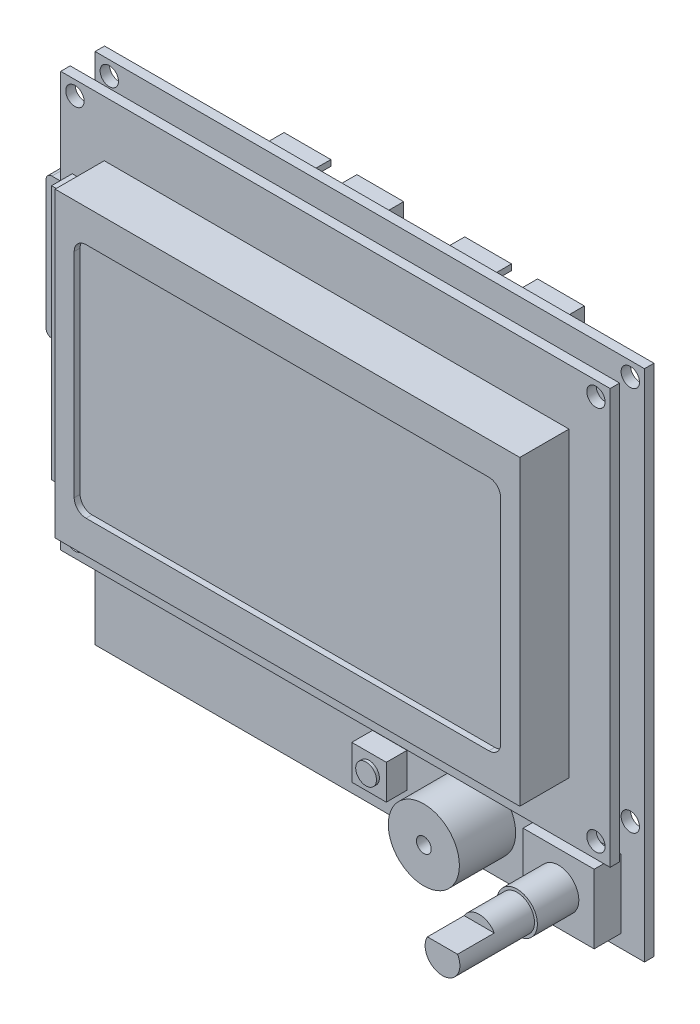
SolidWorks part; units mm, degrees
ref_plane "Front Plane" through (0, 0, 0) normal (0, 0, 1) x (1, 0, 0)
ref_plane "Top Plane" through (0, 0, 0) normal (0, 1, 0) x (1, 0, 0)
ref_plane "Right Plane" through (0, 0, 0) normal (1, 0, 0) x (0, 0, -1)
sketch "Sketch1" plane through (0, 0, 0) normal (0, 0, 1) x (1, 0, 0)
  line L1 (-46.375, -43.375) -> (46.375, -43.375)
  line L2 (-46.375, -43.375) -> (-46.375, 43.375)
  line L3 (-46.375, 43.375) -> (46.375, 43.375)
  line L4 (46.375, -43.375) -> (46.375, 43.375)
  line L6 (-43.975, 40.975) -> (43.975, 40.975) construction
  line L7 (-43.975, 40.975) -> (-43.975, -24.025) construction
  line L8 (-43.975, -24.025) -> (43.975, -24.025) construction
  line L9 (43.975, 40.975) -> (43.975, -24.025) construction
  circle A0 centre (-43.975, 40.975) radius 1.55
  circle A1 centre (43.975, 40.975) radius 1.55
  circle A2 centre (43.975, -24.025) radius 1.55
  circle A3 centre (-43.975, -24.025) radius 1.55
  point P5 (0, 43.375)
  point P6 (-46.375, 0)
  dimension "D3" = 3.1
  dimension "D1" = 86.75
  dimension "D2" = 92.75
  dimension "D4" = 2.4
  dimension "D5" = 2.4
  dimension "D6" = 2.4
  dimension "D7" = 65
extrude "First PCB Extrude" add sketch "Sketch1" along normal blind 1.6
sketch "Sketch2" plane through (0, 0, 1.6) normal (0, 0, 1) x (1, 0, 0)
  line L0 (-46.375, -43.375) -> (46.375, -43.375) construction
  line L1 (-46.375, -43.375) -> (-46.375, 43.375) construction
  circle A0 centre (18.625, -35.375) radius 6
  dimension "D1" = 12
  dimension "D2" = 8
  dimension "D3" = 65
extrude "Speaker Extrude" add sketch "Sketch2" along normal blind 9.5
sketch "Sketch15" plane through (0, 0, 11.1) normal (0, 0, 1) x (1, 0, 0)
  circle A0 centre (18.625, -35.375) radius 1.25
  dimension "D1" = 2.5
extrude "Speaker Hole Cut" cut sketch "Sketch15" against normal blind 5
sketch "Sketch3" plane through (0, 0, 1.6) normal (0, 0, 1) x (-1, 0, 0)
  line L1 (-42.375, 41.2) -> (-30.375, 41.2)
  line L2 (-42.375, 41.2) -> (-42.375, 29.55)
  line L3 (-42.375, 29.55) -> (-30.375, 29.55)
  line L4 (-30.375, 41.2) -> (-30.375, 29.55)
  line L8 (-30.375, 35.375) -> (-18.625, 35.375) construction
  line L10 (-36.375, 41.2) -> (-36.375, 29.55) construction
  line L11 (-46.375, 43.375) -> (-46.375, -43.375) construction
  circle A1 centre (-18.625, 35.375) radius 6 construction
  point P19 (-13.8797, 31.7032)
  dimension "D1" = 11.65
  dimension "D2" = 12
  dimension "D3" = 10
extrude "Rotary Switch Base Extrude" add sketch "Sketch3" along normal blind 4.5
sketch "Sketch4" plane through (0, 0, 1.6) normal (0, 0, 1) x (-1, 0, 0)
  line L0 (-3.375, 38.29) -> (-3.375, 32.46) construction
  line L1 (-6.29, 38.29) -> (-0.46, 38.29)
  line L2 (-6.29, 38.29) -> (-6.29, 32.46)
  line L3 (-6.29, 32.46) -> (-0.46, 32.46)
  line L4 (-0.46, 38.29) -> (-0.46, 32.46)
  line L5 (-6.29, 35.375) -> (-0.46, 35.375) construction
  line L6 (-6.29, 35.375) -> (-18.625, 35.375) construction
  line L15 (-46.375, 43.375) -> (-46.375, -43.375) construction
  point P8 (-3.375, 35.375)
  dimension "D1" = 5.83
  dimension "D2" = 5.83
  dimension "D3" = 43
extrude "Reset Switch Base Extrude" add sketch "Sketch4" along normal blind 3.5
sketch "Sketch5" plane through (0, 0, 5.1) normal (0, 0, 1) x (-1, 0, 0)
  line L1 (-6.29, 38.29) -> (-0.46, 32.46) construction
  line L2 (-0.46, 38.29) -> (-6.29, 32.46) construction
  circle A0 centre (-3.375, 35.375) radius 1.75
  dimension "D1" = 3.5
extrude "Reset Button Extrude" add sketch "Sketch5" along normal blind 0.5
sketch "Sketch16" plane through (0, 0, 6.1) normal (0, 0, 1) x (1, 0, 0)
  line L0 (30.375, -29.55) -> (30.375, -41.2) construction
  line L1 (42.375, -29.55) -> (30.375, -29.55) construction
  circle A0 centre (36.375, -35.375) radius 3.415
  point P4 (30.375, -35.375)
  point P7 (36.375, -29.55)
  dimension "D1" = 6.83
extrude "Rotary Switch Bottom Extrude" add sketch "Sketch16" along normal blind 7
sketch "Sketch17" plane through (0, 0, 13.1) normal (0, 0, 1) x (1, 0, 0)
  circle A0 centre (36.375, -35.375) radius 2.935
  dimension "D1" = 5.87
extrude "Rotary Switch Middle Extrude" add sketch "Sketch17" along normal blind 6.4
sketch "Sketch18" plane through (0, 0, 19.5) normal (0, 0, 1) x (1, 0, 0)
  line L0 (33.8318, -33.91) -> (38.9182, -33.91)
  arc A0 (33.8318, -33.91) -> (38.9182, -33.91) centre (36.375, -35.375) ccw
  circle A1 centre (36.375, -35.375) radius 2.935 construction
  point P6 (36.375, -38.31)
  dimension "D1" = 4.4
extrude "Rotary Switch Top Extrude" add sketch "Sketch18" along normal offset from surface (6.2 mm away) 24.1 up to face at (36.375, -35.375, 1.6) offset beyond the face yes
sketch "Sketch9" plane through (0, 0, 0) normal (0, 0, -1) x (1, 0, 0)
  line L0 (-46.375, -43.375) -> (46.375, -43.375) construction
  line L1 (-46.125, 5.425) -> (-27.875, 5.425)
  line L2 (-46.125, 5.425) -> (-46.125, -20.975)
  line L3 (-46.125, -20.975) -> (-20.375, -20.975)
  line L4 (-20.375, 3.425) -> (-20.375, -20.975)
  line L6 (-20.375, 3.425) -> (-25.875, 3.425)
  line L7 (-25.875, 3.425) -> (-27.875, 5.425)
  line L8 (-46.375, -43.375) -> (-46.375, 43.375) construction
  dimension "D1" = 22.4
  dimension "D2" = 26.4
  dimension "D3" = 0.25
  dimension "D4" = 18.25
  dimension "D5" = 2
  dimension "D6" = 45
  dimension "D7" = 25.75
extrude "SD Card Slot Extrude" add sketch "Sketch9" along normal blind 3
sketch "Sketch19" plane through (0, 0, 1.6) normal (0, 0, 1) x (1, 0, 0)
  line L0 (-46.375, 43.375) -> (-46.375, -43.375) construction
  line L1 (-33.375, -22.875) -> (16.625, -22.875)
  line L2 (-33.375, -22.875) -> (-33.375, -25.375)
  line L3 (-33.375, -25.375) -> (16.625, -25.375)
  line L4 (16.625, -22.875) -> (16.625, -25.375)
  line L5 (-46.375, -43.375) -> (46.375, -43.375) construction
  dimension "D1" = 2.5
  dimension "D2" = 50
  dimension "D3" = 13
  dimension "D4" = 18
extrude "Connector Extrude" add sketch "Sketch19" along normal blind 4.2
sketch "Sketch11" plane through (0, -2, 5.8) normal (0, 0, -1) x (1, 0, 0)
  line L1 (46.375, 24.625) -> (-46.375, 24.625)
  line L2 (46.375, 24.625) -> (46.375, -45.375)
  line L3 (46.375, -45.375) -> (-46.375, -45.375)
  line L4 (-46.375, 24.625) -> (-46.375, -45.375)
  line L8 (46.375, 41.375) -> (46.375, -45.375) construction
  circle A0 centre (-43.975, -42.975) radius 1.55 construction
  circle A1 centre (-43.975, -42.975) radius 1.55
  circle A2 centre (-43.975, 22.025) radius 1.55 construction
  circle A3 centre (43.975, -42.975) radius 1.55 construction
  circle A4 centre (43.975, 22.025) radius 1.55 construction
  circle A5 centre (-43.975, 22.025) radius 1.55
  circle A6 centre (43.975, -42.975) radius 1.55
  circle A7 centre (43.975, 22.025) radius 1.55
  dimension "D2" = 70
extrude "Upper PCB Extrude" add sketch "Sketch11" against normal blind 1.6
sketch "Sketch12" plane through (0, 0, 7.4) normal (0, 0, 1) x (-1, 0, 0)
  line L1 (-39.425, 17.025) -> (39.025, 17.025)
  line L2 (-39.425, 17.025) -> (-39.425, -33.975)
  line L3 (-39.425, -33.975) -> (39.025, -33.975)
  line L4 (39.025, 17.025) -> (39.025, -33.975)
  line L6 (46.375, -43.375) -> (-46.375, -43.375) construction
  line L7 (46.375, 26.625) -> (46.375, -43.375) construction
  dimension "D1" = 51
  dimension "D2" = 78.45
  dimension "D3" = 9.4
  dimension "D4" = 7.35
extrude "LCD Extrude" add sketch "Sketch12" along normal blind 8.3
sketch "Sketch24" plane through (0, 0, 7.4) normal (0, 0, 1) x (1, 0, 0)
  line L0 (-39.025, 33.975) -> (-39.025, -17.025) construction
  line L1 (-39.025, 29.375) -> (-44.425, 29.375)
  line L2 (-39.025, 29.375) -> (-39.025, -13.625)
  line L3 (-39.025, -13.625) -> (-44.425, -13.625)
  line L4 (-44.425, 29.375) -> (-44.425, -13.625)
  line L5 (39.425, 33.975) -> (-39.025, 33.975) construction
  dimension "D1" = 5.4
  dimension "D2" = 43
  dimension "D3" = 4.6
extrude "LCD Bumpout Extrude" add sketch "Sketch24" along normal blind 3.5
sketch "Sketch13" plane through (0, 0, 15.7) normal (0, 0, 1) x (-1, 0, 0)
  line L0 (-0.2, 17.025) -> (-0.2, -33.975) construction
  line L2 (-39.425, -33.975) -> (39.025, -33.975) construction
  line L3 (-39.425, -8.475) -> (39.025, -8.475) construction
  line L4 (-39.425, 17.025) -> (-39.425, -33.975) construction
  line L5 (39.025, -33.975) -> (39.025, 17.025) construction
  line L6 (-0.2, 11.525) -> (-0.2, -28.475) construction
  line L7 (-34.2, 11.525) -> (33.8, 11.525)
  line L8 (-36.2, 9.525) -> (-36.2, -26.475)
  line L9 (-34.2, -28.475) -> (33.8, -28.475)
  line L10 (35.8, 9.525) -> (35.8, -26.475)
  line L11 (-39.425, 17.025) -> (39.025, 17.025) construction
  arc A8 (33.8, 11.525) -> (35.8, 9.525) centre (33.8, 9.525) cw
  arc A9 (-36.2, -26.475) -> (-34.2, -28.475) centre (-34.2, -26.475) ccw
  arc A10 (-34.2, 11.525) -> (-36.2, 9.525) centre (-34.2, 9.525) ccw
  arc A11 (33.8, -28.475) -> (35.8, -26.475) centre (33.8, -26.475) ccw
  point P18 (-0.2, -8.475)
  point P19 (-0.2, -8.475)
  point P62 (-36.2, -28.475)
  point P65 (-36.2, 11.525)
  dimension "D8" = 2
  dimension "D1" = 40
  dimension "D2" = 72
extrude "Screen Recess Extrude" cut sketch "Sketch13" against normal blind 1 contours L10 L7 L8 L9 region at (0.2, 8.475, 15.7)
sketch "Sketch21" plane through (0, 0, 0) normal (0, 0, -1) x (-1, 0, 0)
  line L0 (-46.375, -43.375) -> (-46.375, 43.375) construction
  line L1 (-25.625, 36.875) -> (-5.425, 36.875)
  line L2 (-25.625, 36.875) -> (-25.625, 28.025)
  line L3 (-25.625, 28.025) -> (-5.425, 28.025)
  line L4 (-5.425, 36.875) -> (-5.425, 28.025)
  line L5 (4.875, 36.875) -> (25.075, 36.875)
  line L6 (4.875, 36.875) -> (4.875, 28.025)
  line L7 (4.875, 28.025) -> (25.075, 28.025)
  line L8 (25.075, 36.875) -> (25.075, 28.025)
  line L9 (-46.375, 43.375) -> (46.375, 43.375) construction
  line L10 (-24.625, 35.875) -> (-6.425, 35.875)
  line L11 (-6.425, 35.875) -> (-6.425, 29.025)
  line L12 (-24.625, 29.025) -> (-6.425, 29.025)
  line L13 (-24.625, 35.875) -> (-24.625, 29.025)
  line L14 (5.875, 35.875) -> (24.075, 35.875)
  line L15 (24.075, 35.875) -> (24.075, 29.025)
  line L16 (5.875, 29.025) -> (24.075, 29.025)
  line L17 (5.875, 35.875) -> (5.875, 29.025)
  dimension "D1" = 20.2
  dimension "D2" = 10.3
  dimension "D3" = 8.85
  dimension "D4" = 20.75
  dimension "D5" = 6.5
  dimension "D6" = 1
  dimension "D7" = 1
extrude "Connectors Extrude" add sketch "Sketch21" along normal blind 9
sketch "Sketch22" plane through (0, 0, 0) normal (0, 0, -1) x (-1, 0, 0)
  line L4 (-24.625, 35.875) -> (-24.625, 29.025)
  line L5 (-24.625, 29.025) -> (-6.425, 29.025)
  line L6 (-6.425, 29.025) -> (-6.425, 35.875)
  line L7 (-6.425, 35.875) -> (-24.625, 35.875)
  line L8 (-24.625, 35.875) -> (-24.625, 29.025)
  line L9 (-24.625, 29.025) -> (-6.425, 29.025)
  line L10 (-6.425, 29.025) -> (-6.425, 35.875)
  line L11 (-6.425, 35.875) -> (-24.625, 35.875)
  line L12 (5.875, 35.875) -> (5.875, 29.025)
  line L13 (5.875, 29.025) -> (24.075, 29.025)
  line L14 (24.075, 29.025) -> (24.075, 35.875)
  line L15 (24.075, 35.875) -> (5.875, 35.875)
  line L16 (5.875, 35.875) -> (5.875, 29.025)
  line L17 (5.875, 29.025) -> (24.075, 29.025)
  line L18 (24.075, 29.025) -> (24.075, 35.875)
  line L19 (24.075, 35.875) -> (5.875, 35.875)
  dimension "D1" = 0
  dimension "D2" = 0
extrude "Connector Recess Extrude" add sketch "Sketch22" along normal blind 2.55
sketch "Sketch23" plane through (0, 0, -9) normal (0, 0, -1) x (-1, 0, 0)
  line L0 (-5.425, 36.875) -> (-25.625, 36.875) construction
  line L1 (-17.725, 36.875) -> (-13.325, 36.875)
  line L2 (-17.725, 36.875) -> (-17.725, 35.875)
  line L3 (-17.725, 35.875) -> (-13.325, 35.875)
  line L4 (-13.325, 36.875) -> (-13.325, 35.875)
  line L5 (-6.425, 35.875) -> (-24.625, 35.875) construction
  line L6 (25.075, 36.875) -> (4.875, 36.875) construction
  line L7 (12.775, 36.875) -> (17.175, 36.875)
  line L8 (12.775, 36.875) -> (12.775, 35.875)
  line L9 (12.775, 35.875) -> (17.175, 35.875)
  line L10 (17.175, 36.875) -> (17.175, 35.875)
  line L11 (24.075, 35.875) -> (5.875, 35.875) construction
  line L12 (14.975, 29.025) -> (14.975, 36.875) construction
  line L13 (5.875, 29.025) -> (24.075, 29.025) construction
  line L14 (-15.525, 29.025) -> (-15.525, 36.875) construction
  line L15 (-24.625, 29.025) -> (-6.425, 29.025) construction
  point P20 (14.975, 36.875)
  point P25 (-15.525, 36.875)
  dimension "D1" = 4.4
extrude "Connector Notch Extrude" cut sketch "Sketch23" against normal up to surface (6.45 mm away) up to face at (15.525, 32.45, -2.55)
sketch "Sketch20" plane through (-46.125, 0, 0) normal (-1, 0, 0) x (0, 0, 1)
  line L0 (1.6, 43.375) -> (1.6, -43.375) construction
  line L1 (-2.423, 19.65) -> (-0.27, 19.65)
  line L2 (-2.423, 19.65) -> (-2.423, -4.1)
  line L3 (-2.423, -4.1) -> (-0.27, -4.1)
  line L4 (-0.27, 19.65) -> (-0.27, -4.1)
  line L5 (-3, 7.775) -> (-2.423, 7.775) construction
  line L6 (-3, -5.425) -> (-3, 20.975) construction
  dimension "D1" = 23.75
  dimension "D2" = 2.153
  dimension "D3" = 1.87
extrude "SD Card Extrude" add sketch "Sketch20" along normal blind 10.4
fillet "SD Card Fillet" radius 1 2 edges at (-56.525, -4.1, -1.3465) (-56.525, 19.65, -1.3465)
